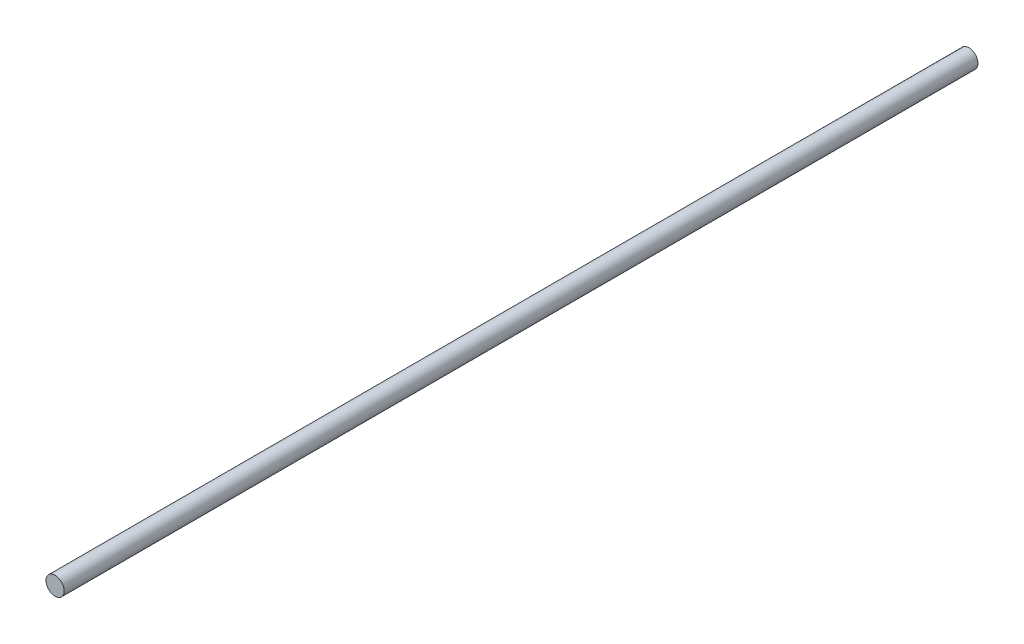
SolidWorks part; units mm, degrees
ref_plane "Plano frontal" through (0, 0, 0) normal (0, 0, 1) x (1, 0, 0)
ref_plane "Plano superior" through (0, 0, 0) normal (0, 1, 0) x (1, 0, 0)
ref_plane "Plano direito" through (0, 0, 0) normal (1, 0, 0) x (0, 0, -1)
sketch "Esboço1" plane through (0, 0, 0) normal (0, 0, 1) x (1, 0, 0)
  circle A0 centre (0, 0) radius 4
  dimension "D1" = 8
extrude "Ressalto-extrusão1" add sketch "Esboço1" along normal mid plane 402
ref_axis "Eixo1" through (0, 0, 201) along (0, 0, -1)
